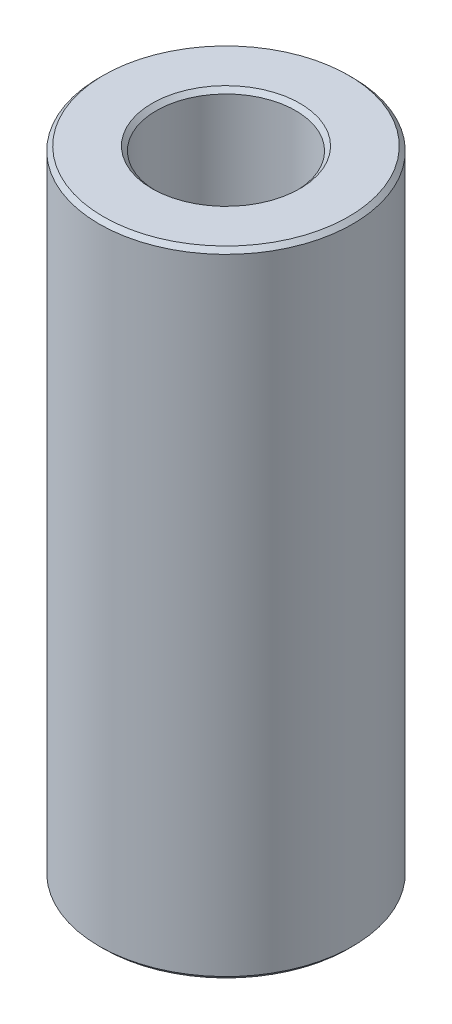
SolidWorks part; units mm, degrees
ref_plane "Front Plane" through (0, 0, 0) normal (0, 0, 1) x (1, 0, 0)
ref_plane "Top Plane" through (0, 0, 0) normal (0, 1, 0) x (1, 0, 0)
ref_plane "Right Plane" through (0, 0, 0) normal (1, 0, 0) x (0, 0, -1)
sketch "Sketch1" plane through (0, 0, 0) normal (0, 1, 0) x (1, 0, 0)
  circle A0 centre (0, 0) radius 6
  dimension "D1" = 12
extrude "Boss-Extrude1" add sketch "Sketch1" along normal blind 30
hole_wizard "M6 Clearance Hole1" positions "Sketch2" profile "Sketch3" hole size "M6" standard "ANSI Metric" end condition through all
sketch "Sketch2" plane through (0, 30, 0) normal (0, 1, 0) x (1, 0, 0)
  point P0 (0, 0)
sketch "Sketch3" plane through (0, 30, 0) normal (1, 0, 0) x (0, 0, 1)
  line L0 (0, 0) -> (0, 30)
  line L1 (0, 30) -> (3.3, 30)
  line L2 (3.3, 30) -> (3.3, 0)
  line L5 (3.3, 0) -> (0, 0)
  line L11 (0, -6.35) -> (0, 107.95) construction
  dimension "Thru Hole Dia." = 6.6
  dimension "Thru Hole Depth" = 30
chamfer "Chamfer1" distance 0.2 angle 45 4 edges at (0, 0, 6) (0, 30, 6) (0, 0, 3.3) (0, 30, 3.3)
